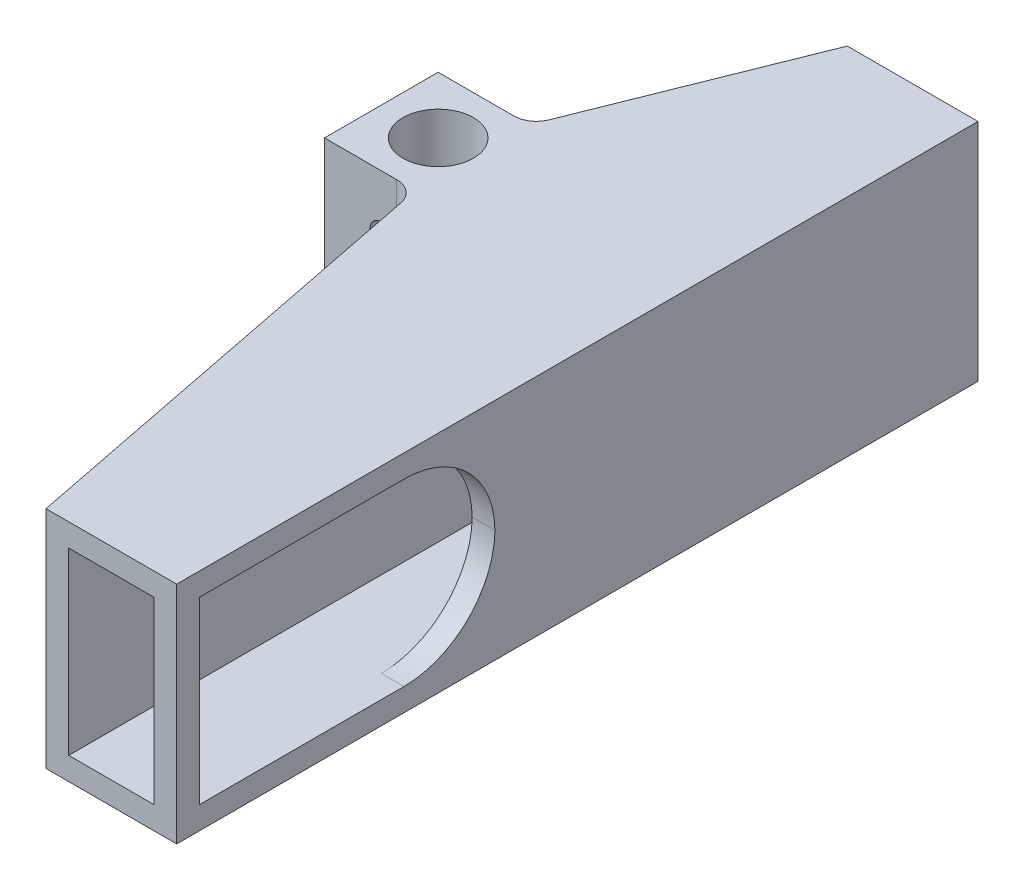
SolidWorks part; units mm, degrees
ref_plane "Alzado" through (0, 0, 0) normal (1, 0, 0) x (0, 1, 0)
ref_plane "Planta" through (0, 0, 0) normal (0, 0, 1) x (0, 1, 0)
ref_plane "Vista lateral" through (0, 0, 0) normal (0, 1, 0) x (-1, 0, 0)
sketch "Croquis1" plane through (0, 0, 0) normal (0, 0, 1) x (0, 1, 0)
  line L1 (-9.9, -5.75) -> (9.9, -5.75)
  line L2 (-9.9, -5.75) -> (-9.9, 5.75)
  line L3 (-9.9, 5.75) -> (9.9, 5.75)
  line L4 (9.9, -5.75) -> (9.9, 5.75)
  line L5 (-9.9, -5.75) -> (9.9, 5.75) construction
  line L6 (-9.9, 5.75) -> (9.9, -5.75) construction
  point P0 (0, 0)
  dimension "D1" = 19.8
  dimension "D2" = 11.5
extrude "Saliente-Extruir1" add sketch "Croquis1" along normal blind 70.5 contours L2 L1 L4 L3
shell "Vaciado1" thickness 2 removed face at (0, 0, 70.5)
sketch "Croquis3" plane through (0, 0, 70.5) normal (0, 0, 1) x (1, 0, 0)
  line L0 (3.75, 7.9) -> (5.75, 7.9)
  line L1 (5.75, -9.9) -> (5.75, 9.9) construction
  line L2 (3.75, -7.9) -> (5.75, -7.9)
sketch "Croquis4" plane through (5.75, 0, 0) normal (1, 0, 0) x (0, 1, 0)
  line L0 (-7.9, 70.5) -> (7.9, 70.5)
  line L1 (-7.9, 70.5) -> (-7.9, 42.5)
  line L2 (7.9, 70.5) -> (7.9, 42.5)
  line L3 (-7.9, 42.5) -> (7.9, 42.5)
  dimension "D1" = 15.8
  dimension "D2" = 28
extrude "Cortar-Extruir1" cut sketch "Croquis4" against normal blind 2
fillet "Redondeo1" radius 8 2 edges at (4.75, 7.9, 42.5) (4.75, -7.9, 42.5)
sketch "Croquis5" plane through (5.75, 0, 0) normal (1, 0, 0) x (0, 1, 0)
  line L0 (-7.9, 70.5) -> (-7.9, 68.5)
  line L1 (-7.9, 70.5) -> (7.9, 70.5)
  line L2 (-7.9, 68.5) -> (7.9, 68.5)
  line L3 (7.9, 70.5) -> (7.9, 68.5)
  line L4 (-7.9, 70.5) -> (-7.9, 50.5) construction
  dimension "D1" = 15.8
  dimension "D2" = 2
extrude "Saliente-Extruir2" add sketch "Croquis5" against normal blind 2 contours L0 L1 L3 L2
sketch "Croquis6" plane through (-5.75, 0, 0) normal (-1, 0, 0) x (0, -1, 0)
  line L0 (-9.9, 20) -> (9.9, 20)
  line L1 (-9.9, 20) -> (-9.9, 30)
  line L2 (9.9, 20) -> (9.9, 30)
  line L3 (-9.9, 30) -> (9.9, 30)
  line L7 (9.9, 0) -> (-9.9, 0) construction
  line L8 (-9.9, 70.5) -> (-9.9, 0) construction
  line L9 (9.9, 70.5) -> (9.9, 0) construction
  dimension "D1" = 10
  dimension "D2" = 20
extrude "Saliente-Extruir4" add sketch "Croquis6" along normal blind 16
sketch "Croquis9" plane through (0, -9.9, 0) normal (0, -1, 0) x (1, 0, 0)
  line L0 (-5.75, 70.5) -> (-13.75, 30)
  line L1 (-21.75, 30) -> (-5.75, 30) construction
  line L2 (-13.75, 30) -> (-5.75, 30)
  line L3 (-5.75, 30) -> (-5.75, 70.5)
  line L4 (-5.75, 0) -> (-13.75, 20)
  line L5 (-21.75, 20) -> (-5.75, 20) construction
  line L6 (-13.75, 20) -> (-5.75, 20)
  line L7 (-5.75, 20) -> (-5.75, 0)
extrude "Saliente-Extruir5" add sketch "Croquis9" against normal blind 19.8
sketch "Croquis10" plane through (0, -9.9, 0) normal (0, -1, 0) x (1, 0, 0)
  line L0 (-21.75, 20) -> (-21.75, 30) construction
  circle A0 centre (-16.7453, 25) radius 3.1
  point P5 (-21.75, 25)
  dimension "D1" = 6.2
  dimension "D2" = 5.0047
extrude "Cortar-Extruir4" cut sketch "Croquis10" against normal blind 19.8
fillet "Redondeo2" [suppressed] radius 10
fillet "Redondeo3" radius 2 2 edges at (-13.75, 0, 20) (-13.75, 0, 30)
ref_plane "Plano1" through (0, 0, 25) normal (0, 0, 1) x (0, -1, 0)
sketch "Croquis11" plane through (0, 0, 25) normal (0, 0, 1) x (0, -1, 0)
  line L0 (12.1743, -16.7453) -> (-9.9, -16.7453) construction
  line L1 (-9.9, -13.6453) -> (-9.9, -19.8453) construction
  line L2 (9.9, -19.8453) -> (9.9, -13.6453) construction
  circle A0 centre (-5, -16.7453) radius 1
  circle A1 centre (5, -16.7453) radius 1
  point P8 (-9.9, -16.7453)
  point P9 (0, 0)
  point P10 (0, 0)
  dimension "D1" = 2
  dimension "D2" = 10
  dimension "D3" = 4.9
  dimension "D4" = 4.9
extrude "Cortar-Extruir5" cut sketch "Croquis11" against normal through all both and the other way through all
equation "\"15.8mm.\"=19.8"
